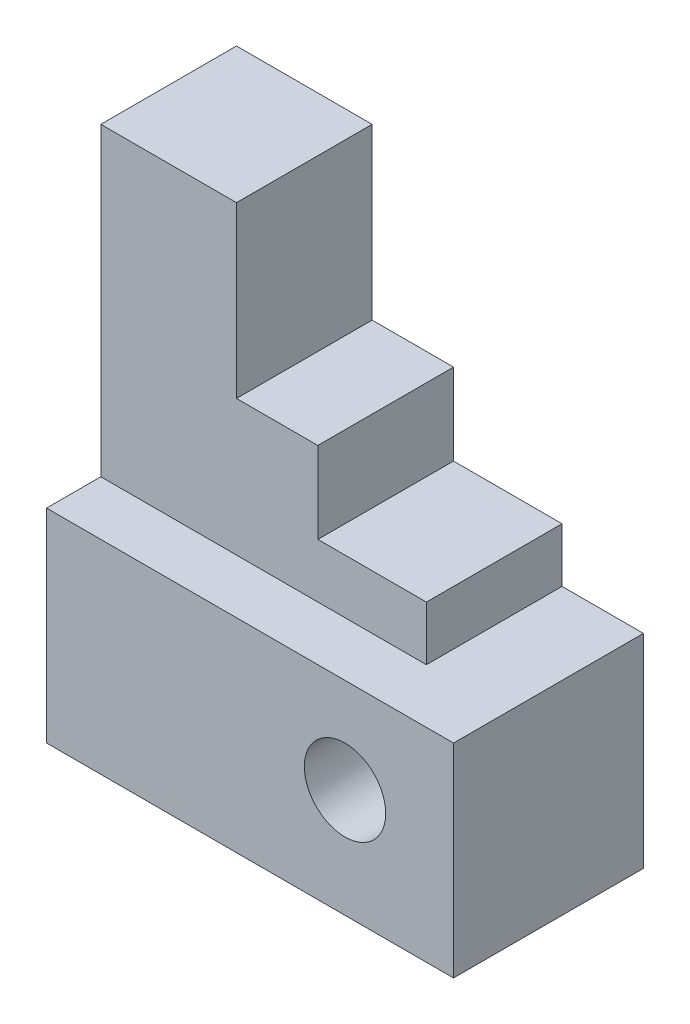
SolidWorks part; units mm, degrees
ref_plane "Front Plane" through (0, 0, 0) normal (0, 0, 1) x (1, 0, 0)
ref_plane "Top Plane" through (0, 0, 0) normal (0, 1, 0) x (1, 0, 0)
ref_plane "Right Plane" through (0, 0, 0) normal (1, 0, 0) x (0, 0, -1)
sketch "Sketch1" plane through (0, 0, 0) normal (0, 0, 1) x (1, 0, 0)
  line L0 (0, 30) -> (0, 75)
  line L1 (0, 0) -> (60, 0)
  line L2 (0, 0) -> (0, 30)
  line L3 (0, 30) -> (60, 30)
  line L4 (60, 0) -> (60, 30)
  line L5 (0, 75) -> (20, 75)
  line L6 (20, 75) -> (20, 50)
  line L7 (20, 50) -> (32, 50)
  line L8 (32, 50) -> (32, 38)
  line L9 (32, 38) -> (48, 38)
  line L10 (48, 38) -> (48, 30)
  circle A0 centre (44, 16) radius 6
  point P14 (32, 44)
  dimension "D4" = 12
  dimension "D1" = 60
  dimension "D2" = 75
  dimension "D3" = 30
  dimension "D5" = 16
  dimension "D6" = 16
  dimension "D7" = 12
  dimension "D8" = 20
  dimension "D9" = 12
  dimension "D10" = 12
  dimension "D11" = 20
extrude "Boss-Extrude1" add sketch "Sketch1" along normal blind 28 contours L1 L4 L3 L2 A0 region at (29.0614, 14.933, 0)
extrude "Boss-Extrude2" add sketch "Sketch1<3>" along normal blind 20 contours L10 L9 L8 L7 L6 L5 L0 L3 region at (16.0568, 48.2666, 0)
sketch "Sketch1<3>" plane through (0, 0, 0) normal (0, 0, 1) x (1, 0, 0) same geometry as "Sketch1"
